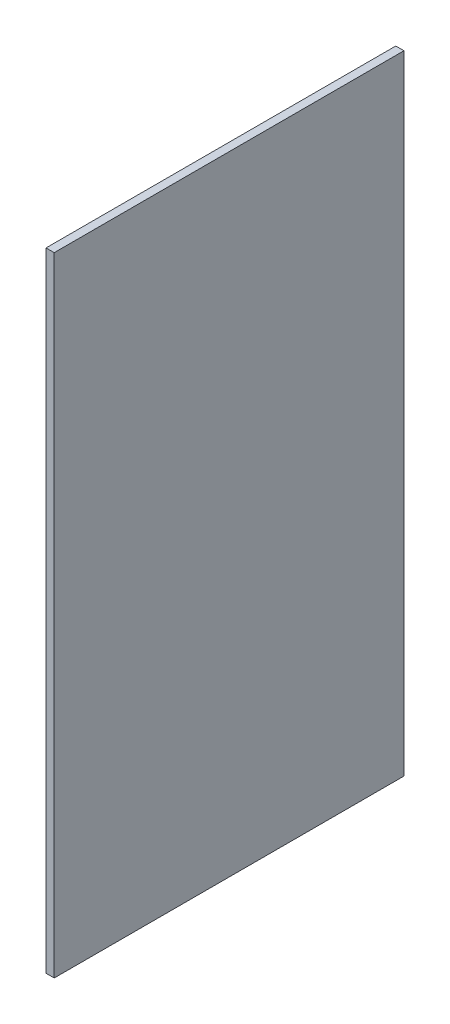
SolidWorks part; units mm, degrees
material "Pine"
ref_plane "Front Plane" through (0, 0, 0) normal (0, 0, 1) x (1, 0, 0)
ref_plane "Top Plane" through (0, 0, 0) normal (0, 1, 0) x (1, 0, 0)
ref_plane "Right Plane" through (0, 0, 0) normal (1, 0, 0) x (0, 0, -1)
sketch "Sketch1" plane through (0, 0, 0) normal (0, 0, 1) x (1, 0, 0)
  line L0 (-108.5345, -3.9032) -> (-108.5345, 1456.1455)
  line L1 (-89.4845, -3.9032) -> (-89.4845, 1456.1455)
  line L2 (-108.5345, -3.9032) -> (-89.4845, -3.9032)
  line L3 (-108.5345, 1456.1455) -> (-89.4845, 1456.1455)
  dimension "D1" = 19.05
extrude "Boss-Extrude1" add sketch "Sketch1" along normal blind 812.8
